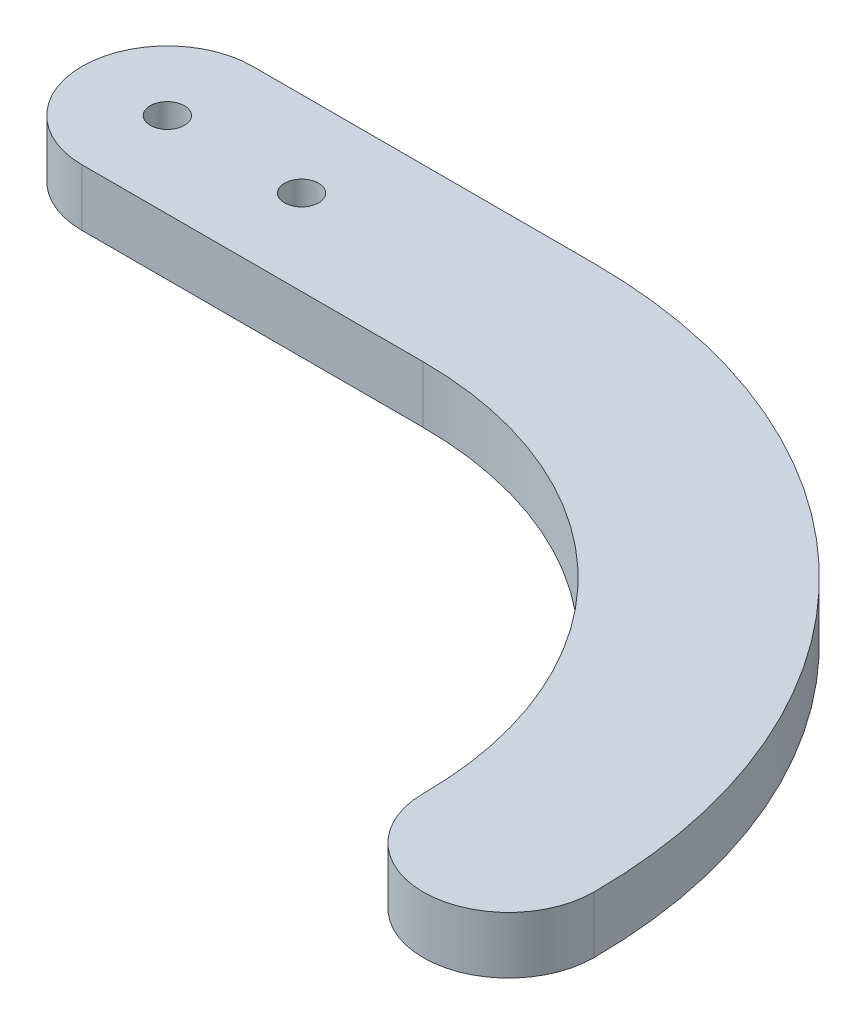
SolidWorks part; units mm, degrees
ref_plane "Front" through (0, 0, 0) normal (0, 0, 1) x (1, 0, 0)
ref_plane "Top" through (0, 0, 0) normal (0, 1, 0) x (1, 0, 0)
ref_plane "Right" through (0, 0, 0) normal (1, 0, 0) x (0, 0, -1)
sketch "Sketch1" plane through (0, 0, 0) normal (0, 1, 0) x (1, 0, 0)
  line L0 (0, 0) -> (30, 0) construction
  line L1 (0, 7.5) -> (30, 7.5)
  line L2 (0, -7.5) -> (30, -7.5)
  line L3 (62.875, -40.375) -> (77.875, -40.375) construction
  arc A0 (0, 7.5) -> (0, -7.5) centre (0, 0) ccw
  arc A5 (30, -7.5) -> (30, 7.5) centre (30, 0) ccw
  arc A6 (30, 0) -> (70.375, -40.375) centre (30, -40.375) cw construction
  arc A7 (77.875, -40.375) -> (30, 7.5) centre (30, -40.375) ccw
  arc A8 (62.875, -40.375) -> (30, -7.5) centre (30, -40.375) ccw
  arc A9 (62.875, -40.375) -> (77.875, -40.375) centre (70.375, -40.375) ccw
  arc A10 (30, 7.5) -> (30, -7.5) centre (30, 0) ccw
  circle A11 centre (0, 0) radius 1.5
  circle A12 centre (11.8, 0) radius 1.5
  point P2 (15, 0)
  point P12 (58.5494, -11.8256)
  dimension "D1" = 30
  dimension "D2" = 7.5
  dimension "D3" = 32.875
  dimension "D4" = 11.8
  dimension "D5" = 3
extrude "Boss-Extrude1" add sketch "Sketch1" along normal blind 5 contours A10 L1 A0 L2 A12 A11 | A5 A10 | A8 A9 A7 A5 region at (9.2136, 0, 0) region at (59.4535, 0, 18.4215) region at (30, 0, 0)
